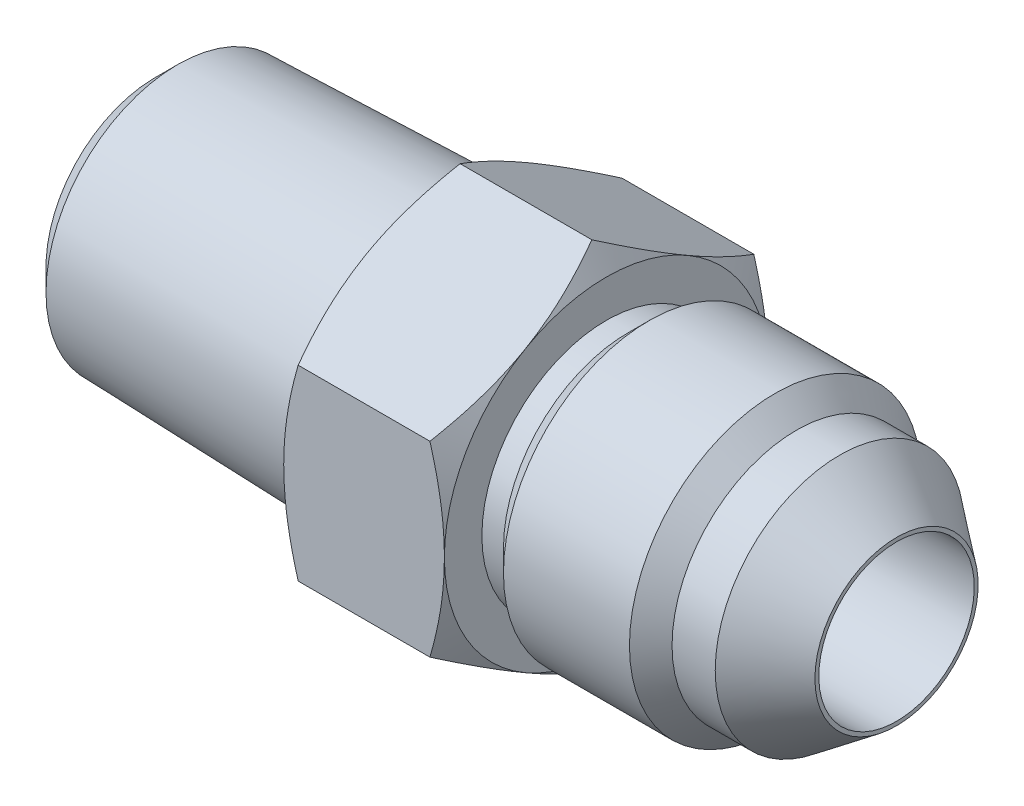
SolidWorks part; units mm, degrees
material "AISI 316 Stainless Steel Sheet (SS)"
ref_plane "Front" through (0, 0, 0) normal (0, 0, 1) x (1, 0, 0)
ref_plane "Top" through (0, 0, 0) normal (0, 1, 0) x (1, 0, 0)
ref_plane "Right" through (0, 0, 0) normal (1, 0, 0) x (0, 0, -1)
sketch "Sketch6" plane through (0, 0, 0) normal (0, 0, 1) x (1, 0, 0)
  line L0 (-3.937, 6.858) -> (-3.937, -6.858) construction
  line L1 (18.161, 7.1438) -> (18.161, -7.1438) construction
  line L2 (-18.161, 0) -> (18.161, 0)
  line L4 (-18.161, 0) -> (-18.161, 7.1438)
  line L5 (-18.161, 7.1438) -> (18.161, 7.1438)
  line L6 (18.161, 0) -> (18.161, 7.1438)
  line L7 (-18.161, 3.556) -> (-18.161, -3.556) construction
  line L8 (-3.937, 8.6995) -> (-3.937, -8.6995) construction
  line L9 (3.937, 8.6995) -> (3.937, -8.6995) construction
  point P4 (3.937, 0)
  point P6 (-3.937, 0)
  dimension "Straight Dia" = 14.2875
  dimension "Length" = 36.322
  dimension "L1" = 14.224
  dimension "Pipe OD" = 13.716
  dimension "L2" = 14.224
  dimension "D1" = 7.112
  dimension "D2" = 17.399
revolve "Revolve3" add sketch "Sketch6" angle 360 about L2
sketch "Sketch14" plane through (18.161, 0, 0) normal (-1, 0, 0) x (0, 0, 1)
  circle A1 centre (0, 0) radius 7.1438
  circle A2 centre (0, 0) radius 7.1438
  dimension "D1" = 0
curve "Helix/Spiral1" pitch 1.4111 height 15.6351 turns 11.08 parameters "Pitch"=1.4111
sketch "Sketch15" plane through (0, 0, 0) normal (0, 0, 1) x (1, 0, 0)
  line L0 (18.161, 7.1438) -> (19.3957, 7.1438)
  line L1 (19.3957, 7.1438) -> (18.8666, 6.2272)
  line L2 (18.8666, 6.2272) -> (18.6902, 6.2272)
  line L3 (18.6902, 6.2272) -> (18.161, 7.1438)
  line L4 (18.7784, 6.2272) -> (18.7784, 7.1438) construction
  line L5 (18.4256, 6.6855) -> (19.1311, 6.6855) construction
  dimension "D1" = 60
  dimension "D2" = 0.1764
  dimension "D3" = 0.7056
sweep "Cut-Sweep1" [suppressed] cut profiles "Sketch15" path "Helix/Spiral1"
ref_plane "Plane1" through (-3.937, 0, 0) normal (1, 0, 0) x (0, 0, -1)
sketch "Sketch12" plane through (-3.937, 0, 0) normal (1, 0, 0) x (0, 0, -1)
  line L1 (0, 9.1654) -> (-7.9375, 4.5827)
  line L2 (-7.9375, 4.5827) -> (-7.9375, -4.5827)
  line L3 (-7.9375, -4.5827) -> (0, -9.1654)
  line L4 (0, -9.1654) -> (7.9375, -4.5827)
  line L5 (7.9375, -4.5827) -> (7.9375, 4.5827)
  line L6 (7.9375, 4.5827) -> (0, 9.1654)
  circle A0 centre (0, 0) radius 7.9375 construction
  dimension "Hex" = 15.875
extrude "Extrude1" add sketch "Sketch12" along normal up to vertex (7.874 mm away) up to point (3.937, 0, 0)
sketch "Sketch7" plane through (0, 0, 0) normal (0, 0, 1) x (1, 0, 0)
  line L0 (-18.161, 0) -> (-18.161, 3.81)
  line L2 (-18.161, 3.81) -> (18.161, 3.81)
  line L4 (18.161, 0) -> (18.161, 7.1438) construction
  line L11 (18.161, 3.81) -> (18.161, 0)
  line L12 (18.161, 0) -> (-18.161, 0)
  line L13 (-18.161, 3.81) -> (-18.161, -3.81) construction
  dimension "ID" = 7.62
sketch "Sketch10" plane through (0, 0, 0) normal (0, 0, 1) x (1, 0, 0)
  line L0 (-18.161, 7.1438) -> (18.161, 7.1438) construction
  line L1 (18.161, 7.1438) -> (19.3957, 7.1438) construction
  line L2 (-3.937, -6.858) -> (-18.161, -6.4233) construction
  line L3 (3.937, 9.1654) -> (3.937, 4.5827) construction
  line L5 (0, 0) -> (-18.161, 0) construction
  line L6 (6.0389, 7.1438) -> (3.937, 7.1438)
  line L9 (3.937, 6.1002) -> (3.937, 7.1438)
  line L21 (18.161, 7.1438) -> (12.2144, 7.1438)
  line L22 (12.2144, 7.1438) -> (13.2579, 6.1002)
  line L23 (13.2579, 6.1002) -> (15.3746, 6.1002)
  line L24 (15.3746, 6.1002) -> (18.161, 4.0005)
  line L25 (18.161, 4.0005) -> (18.161, 7.1438)
  line L26 (4.9953, 6.1002) -> (3.937, 6.1002)
  line L27 (6.0389, 7.1438) -> (4.9953, 6.1002)
  point P5 (10.4357, -7.1438)
  point P9 (-11.811, -6.6174)
  dimension "D1" = 8.001
  dimension "D2" = 37
  dimension "D3" = 2.1167
  dimension "D5" = 45
  dimension "D4" = 1.0583
  dimension "D6" = 2.8222
  dimension "D7" = 0.127
  dimension "D9" = 6.35
  dimension "D8" = 1.75
revolve "Cut-Revolve6" cut sketch "Sketch10" angle 360 about L2
revolve "Cut-Revolve5" cut sketch "Sketch7" angle 360 about L12
sketch "Sketch13" plane through (0, 0, 0) normal (0, 0, 1) x (1, 0, 0)
  line L0 (-3.937, 9.1654) -> (-3.937, 7.9375)
  line L1 (-3.937, 4.5827) -> (-3.937, 9.1654) construction
  line L2 (-3.937, 7.9375) -> (-3.2281, 9.1654)
  line L3 (-3.2281, 9.1654) -> (-3.937, 9.1654)
  line L4 (3.2281, 9.1654) -> (3.937, 7.9375)
  line L5 (3.937, 9.1654) -> (3.937, 4.5827) construction
  line L6 (3.937, 7.9375) -> (3.937, 9.1654)
  line L7 (3.937, 9.1654) -> (3.2281, 9.1654)
  dimension "D2" = 30
revolve "Cut-Revolve7" cut sketch "Sketch13" angle 360 about L2
sketch "Sketch17" plane through (-18.161, 0, 0) normal (-1, 0, 0) x (0, 0, 1)
  circle A0 centre (0, 0) radius 7.1438 construction
  circle A1 centre (0, 0) radius 7.1438
extrude "Cut-Extrude1" cut sketch "Sketch17" against normal up to vertex (14.224 mm away) up to point (-3.937, 0, 0)
ref_plane "Plane2" through (-3.937, 0, 0) normal (1, 0, 0) x (0, 0, -1)
sketch "Sketch19" plane through (-3.937, 0, 0) normal (1, 0, 0) x (0, 0, -1)
  circle A0 centre (0, 0) radius 6.858
extrude "Boss-Extrude1" add sketch "Sketch19" against normal up to vertex (14.224 mm away) draft 1.75 separate body up to point (-18.161, 0, 0)
sketch "Sketch20" plane through (-18.161, 0, 0) normal (1, 0, 0) x (0, 0, -1)
  circle A1 centre (0, 0) radius 6.4234
  circle A2 centre (0, 0) radius 6.4234 construction
sketch "Sketch21" plane through (0, 0, 0) normal (0, 0, 1) x (1, 0, 0)
  line L0 (-19.3641, 6.3033) -> (-18.2303, 6.3033) construction
  line L1 (-19.5028, 6.5435) -> (-18.7972, 5.3215) construction
  line L2 (-18.9173, 5.5295) -> (-18.6771, 5.5295)
  line L3 (-18.7972, 5.3215) -> (-18.0917, 6.5435) construction
  line L4 (-18.7972, 5.3215) -> (-18.6771, 5.5295) construction
  line L5 (-18.7972, 6.3033) -> (-18.7972, 6.5435) construction
  line L6 (-19.5028, 6.5435) -> (-18.0917, 6.5435) construction
  line L7 (-18.7972, 6.4234) -> (-18.161, 6.4234) construction
  line L8 (-18.0917, 6.5435) -> (-19.4334, 6.4234)
  line L9 (-19.4334, 6.4234) -> (-18.9173, 5.5295)
  line L10 (-18.6771, 5.5295) -> (-18.0917, 6.5435)
  line L11 (-18.7972, 5.3215) -> (-18.7972, 5.5295) construction
  dimension "D2" = 0.2402
  dimension "D1" = 1.4111
curve "Helix/Spiral2" [suppressed] parameters "Pitch"=1.4111
chamfer "Chamfer1" distance 1.0583 angle 45 1 edges at (-18.161, 0, -6.4234) first distance on face at (-18.161, 0, -6.4234)
sketch "Sketch22" plane through (-3.937, 0, 0) normal (1, 0, 0) x (0, 0, -1)
  circle A1 centre (0, 0) radius 6.858
  circle A2 centre (0, 0) radius 6.858
  dimension "D1" = 0
sweep "Cut-Sweep2" [suppressed] cut profiles "Sketch21" path "Helix/Spiral2"
extrude "Boss-Extrude3" add sketch "Sketch22" against normal up to vertex (14.224 mm away) draft 15 up to point (-18.161, 7.1438, 0)
combine bodies "Combine1" operation type add bodies to combine 173 169
sketch "Sketch23" plane through (-18.161, 0, 0) normal (-1, 0, 0) x (0, 0, 1)
  circle A2 centre (0, 0) radius 3.556
extrude "Cut-Extrude2" cut sketch "Sketch23" against normal up to vertex (14.224 mm away) up to point (-3.937, 0, 0)
equation "\"D3@Helix/Spiral1\" = \"L1@Sketch6\"+\"Pitch@Helix/Spiral1\""
equation "\"D2@Sketch15\" = \"Pitch@Helix/Spiral1\"*.125"
equation "\"D3@Sketch15\" = \"Pitch@Helix/Spiral1\"*.5"
equation "\"D3@Sketch10\" = \"Pitch@Helix/Spiral1\"*1.5"
equation "\"D1@Sketch10\" = \"ID@Sketch7\"*1.05"
equation "\"D1@Sketch21\" = \"Pitch@Helix/Spiral2\""
equation "\"D3@Helix/Spiral2\" = \"L2@Sketch6\"+\"Pitch@Helix/Spiral2\""
equation "\"D1@Chamfer1\" = \"Pitch@Helix/Spiral2\"*.75"
equation "\"D4@Sketch10\" = \"Pitch@Helix/Spiral1\"*.75"
equation "\"D6@Sketch10\" = \"Pitch@Helix/Spiral1\"*2"
equation "\"D9@Sketch10\" = \"Pitch@Helix/Spiral2\"*4.5"
equation "\"D2@Sketch6\" = \"Hex@Sketch12\"+.06"
